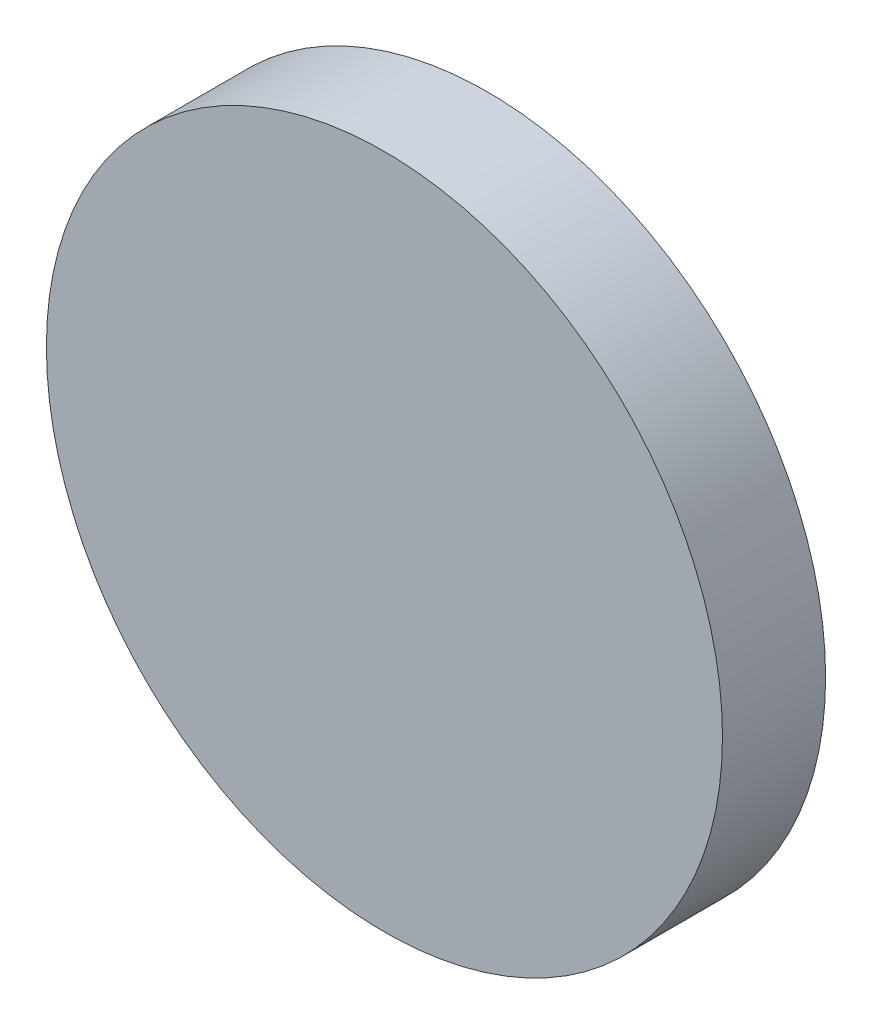
SolidWorks part; units mm, degrees
ref_plane "Front Plane" through (0, 0, 0) normal (0, 0, 1) x (1, 0, 0)
ref_plane "Top Plane" through (0, 0, 0) normal (0, 1, 0) x (1, 0, 0)
ref_plane "Right Plane" through (0, 0, 0) normal (1, 0, 0) x (0, 0, -1)
ref_axis "X-Axis" through (-88.99, 0, 0) along (1, 0, 0)
ref_axis "Y-Axis" through (0, 55, 0) along (0, -1, 0)
ref_axis "Z-Axis" through (0, 0, -88.99) along (0, 0, 1)
sketch "Sketch1" plane through (0, 0, 0) normal (0, 0, 1) x (1, 0, 0)
  circle A0 centre (0, 0) radius 2.95
  dimension "D1" = 5.9
extrude "Boss-Extrude1" add sketch "Sketch1" along normal blind 0.9
